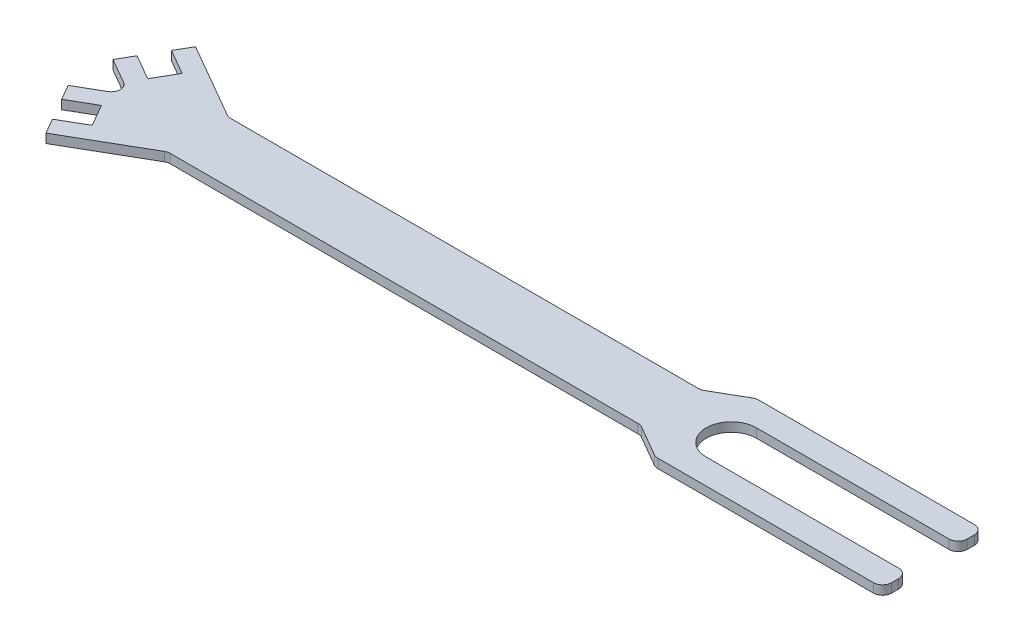
SolidWorks part; units mm, degrees
ref_plane "Front Plane" through (0, 0, 0) normal (0, 0, 1) x (1, 0, 0)
ref_plane "Top Plane" through (0, 0, 0) normal (0, 1, 0) x (1, 0, 0)
ref_plane "Right Plane" through (0, 0, 0) normal (1, 0, 0) x (0, 0, -1)
sketch "Sketch1" plane through (0, 0, 0) normal (0, 1, 0) x (1, 0, 0)
  line L0 (-363.1089, 480) -> (-363.1089, -480)
  line L1 (-363.1089, -480) -> (-303.1089, -480)
  line L2 (-303.1089, -480) -> (-303.1089, -400)
  line L3 (-303.1089, -400) -> (303.1089, -50)
  line L4 (303.1089, -50) -> (1036.8911, -50)
  line L5 (1036.8911, -50) -> (1036.8911, 50) construction
  line L6 (1036.8911, 50) -> (303.1089, 50)
  line L7 (303.1089, 50) -> (-303.1089, 400)
  line L8 (-303.1089, 400) -> (-303.1089, 480)
  line L9 (-303.1089, 480) -> (-363.1089, 480)
  line L10 (-363.1089, 0) -> (1036.8911, 0) construction
  line L11 (0, 225) -> (0, -225) construction
  line L14 (1036.8911, 50) -> (1066.8911, 50)
  line L15 (1036.8911, 50) -> (1036.8911, -50) construction
  line L16 (1036.8911, -50) -> (1066.8911, -50)
  line L17 (1066.8911, 50) -> (1066.8911, -50)
  dimension "D1" = 960
  dimension "D2" = 60
  dimension "D3" = 100
  dimension "D4" = 1400
  dimension "D5" = 150
  dimension "D6" = 80
  dimension "D7" = 30
extrude "Boss-Extrude1" add sketch "Sketch1" along normal blind 9
sketch "Sketch2" plane through (0, 9, 0) normal (0, 1, 0) x (1, 0, 0)
  line L1 (-363.1089, 480) -> (-303.1089, 480)
  line L2 (-363.1089, 480) -> (-363.1089, 400)
  line L3 (-363.1089, 400) -> (-303.1089, 400)
  line L4 (-303.1089, 480) -> (-303.1089, 400)
  line L5 (-363.1089, -480) -> (-303.1089, -480)
  line L6 (-363.1089, -480) -> (-363.1089, -400)
  line L7 (-363.1089, -400) -> (-303.1089, -400)
  line L8 (-303.1089, -480) -> (-303.1089, -400)
extrude "Boss-Extrude2" add sketch "Sketch2" along normal blind 500
sketch "Sketch3" plane through (0, 0, 0) normal (0, 0, 1) x (1, 0, 0)
  line L0 (-333.1089, 509) -> (-333.1089, 254.2) construction
  line L1 (-363.1089, 509) -> (-303.1089, 509) construction
  line L2 (-333.1089, 254.2) -> (-333.1089, 25) construction
  line L3 (-333.1089, 25) -> (-333.1089, 0) construction
  line L4 (-363.1089, 0) -> (-303.1089, 0) construction
  line L6 (-363.1089, 509) -> (-303.1089, 509)
  line L7 (-363.1089, 509) -> (-363.1089, 9)
  line L8 (-363.1089, 9) -> (-303.1089, 9)
  line L9 (-303.1089, 509) -> (-303.1089, 9)
  circle A0 centre (-333.1089, 254.2) radius 229.2
  circle A1 centre (-333.1089, 254.2) radius 6
  circle A2 centre (-333.1089, 254.2) radius 30
  dimension "D1" = 458.4
  dimension "D3" = 12
  dimension "D2" = 25
extrude "Cut-Extrude1" cut sketch "Sketch3" against normal through all both and the other way through all contours A2 L9 A0 L7 | A0 L9 L6 L7 | A1 region at (-333.1089, 495.8654, 0) region at (-333.1089, 380.1444, 0) region at (-333.1089, 254.2, 0)
sketch "Sketch4" plane through (0, 9, 0) normal (0, 1, 0) x (1, 0, 0)
  line L0 (866.8911, 25) -> (1066.8911, 25)
  line L2 (866.8911, -25) -> (1066.8911, -25)
  line L3 (1066.8911, -25) -> (1066.8911, 25)
  line L4 (866.8911, 0) -> (1066.8911, 0) construction
  line L5 (1066.8911, -50) -> (1066.8911, 50) construction
  circle A0 centre (866.8911, 0) radius 25
  dimension "D1" = 50
  dimension "D2" = 200
extrude "Cut-Extrude2" cut sketch "Sketch4" against normal through all contours L4 A0 L2 | A0 L4 L3 L0 | A0 region at (976.6223, 9, -12.7057) region at (884.0688, 9, -17.1777) region at (976.6223, 9, 12.7057)
sketch "Sketch16" plane through (0, 0, 0) normal (0, 0, 1) x (1, 0, 0)
  line L0 (-359.656, 240.2268) -> (-348.1089, 218.2888)
  line L5 (-348.1089, 218.2888) -> (-348.1089, 24)
  line L7 (-363.1089, 9) -> (-288.1089, 9)
  line L8 (303.1089, 9) -> (-303.1089, 9) construction
  line L9 (-303.1089, 254.2) -> (-303.1089, 24)
  line L10 (-348.1089, 24) -> (-363.1089, 9)
  line L11 (-303.1089, 254.2) -> (-303.1089, 9) construction
  line L12 (-303.1089, 24) -> (-288.1089, 9)
  line L13 (-348.1089, 24) -> (-303.1089, 24) construction
  line L14 (-346.3825, 247.2134) -> (-358.4836, 270.2039)
  line L15 (-319.8353, 261.1866) -> (-331.9364, 284.1771)
  circle A0 centre (-333.1089, 254.2) radius 15
  circle A1 centre (-333.1089, 254.2) radius 30
  arc A2 (-303.1089, 254.2) -> (-363.1089, 254.2) centre (-333.1089, 254.2) ccw construction
  circle A3 centre (-360.6089, 215.2) radius 12.5 construction
  dimension "D1" = 30
  dimension "D4" = 25
  dimension "D2" = 45
  dimension "D3" = 45
extrude "Boss-Extrude8" add sketch "Sketch16" along normal blind 305 and the other way blind 305 contours A1 L0 L5 L10 L7 L12 L9 | A1 L15 A0 L14 region at (-325.4564, 117.1914, 0) region at (-362.2383, 255.3393, 0)
sketch "Sketch17" plane through (0, 0, 0) normal (1, 0, 0) x (0, 0, -1)
  line L1 (230, 309) -> (-230, 309)
  line L2 (230, 309) -> (230, 9)
  line L3 (230, 9) -> (-230, 9)
  line L4 (-230, 309) -> (-230, 9)
  line L5 (0, 0) -> (0, 309) construction
  line L6 (480, 0) -> (-480, 0) construction
  dimension "D1" = 460
  dimension "D2" = 9
  dimension "D3" = 300
extrude "Cut-Extrude9" cut sketch "Sketch17" against normal through all
sketch "Sketch7" plane through (0, 0, 0) normal (1, 0, 0) x (0, 0, -1)
  line L1 (480, 284.2) -> (230, 284.2)
  line L2 (480, 284.2) -> (480, 9)
  line L3 (480, 9) -> (230, 9)
  line L4 (230, 284.2) -> (230, 9)
  line L5 (230, 218.2888) -> (230, 24) construction
  line L6 (471, 146.6) -> (444.5, 146.6) construction
  line L7 (480, 284.2) -> (471, 284.2)
  line L8 (480, 284.2) -> (480, 9)
  line L9 (480, 9) -> (471, 9)
  line L10 (471, 284.2) -> (471, 9)
  line L11 (400, 9) -> (409, 9)
  line L12 (400, 9) -> (400, 284.2)
  line L13 (400, 284.2) -> (409, 284.2)
  line L14 (409, 9) -> (409, 284.2)
  line L15 (444.5, 284.2) -> (435.5, 284.2)
  line L16 (444.5, 284.2) -> (444.5, 9)
  line L17 (444.5, 9) -> (435.5, 9)
  line L18 (435.5, 284.2) -> (435.5, 9)
  line L19 (444.5, 146.6) -> (435.5, 146.6) construction
  line L20 (435.5, 146.6) -> (409, 146.6) construction
  line L22 (0, 274.5241) -> (0, -136.9768) construction
  line L23 (-435.5, 146.6) -> (-409, 146.6) construction
  line L24 (305, 284.2) -> (296, 284.2)
  line L25 (305, 284.2) -> (305, 9)
  line L26 (305, 9) -> (296, 9)
  line L27 (296, 284.2) -> (296, 9)
  line L28 (239, 9) -> (230, 9)
  line L29 (239, 9) -> (239, 284.2)
  line L30 (239, 284.2) -> (230, 284.2)
  line L31 (230, 9) -> (230, 284.2)
  line L32 (-444.5, 146.6) -> (-435.5, 146.6) construction
  line L33 (-471, 146.6) -> (-444.5, 146.6) construction
  line L34 (-230, 9) -> (-230, 284.2)
  line L35 (-239, 284.2) -> (-230, 284.2)
  line L36 (-239, 9) -> (-239, 284.2)
  line L37 (-239, 9) -> (-230, 9)
  line L38 (-296, 284.2) -> (-296, 9)
  line L39 (-305, 9) -> (-296, 9)
  line L40 (-305, 284.2) -> (-305, 9)
  line L41 (-305, 284.2) -> (-296, 284.2)
  line L42 (-435.5, 284.2) -> (-435.5, 9)
  line L43 (-444.5, 9) -> (-435.5, 9)
  line L44 (-444.5, 284.2) -> (-444.5, 9)
  line L45 (-444.5, 284.2) -> (-435.5, 284.2)
  line L46 (-409, 9) -> (-409, 284.2)
  line L47 (-400, 284.2) -> (-409, 284.2)
  line L48 (-400, 9) -> (-400, 284.2)
  line L49 (-400, 9) -> (-409, 9)
  line L50 (-471, 284.2) -> (-471, 9)
  line L51 (-480, 9) -> (-471, 9)
  line L52 (-480, 284.2) -> (-480, 9)
  line L53 (-480, 284.2) -> (-471, 284.2)
  line L54 (-230, 284.2) -> (-230, 9)
  line L55 (-480, 9) -> (-230, 9)
  line L56 (-480, 284.2) -> (-480, 9)
  line L57 (-480, 284.2) -> (-230, 284.2)
  line L58 (305, 218.2888) -> (305, 24) construction
  dimension "D1" = 9
  dimension "D2" = 9
  dimension "D3" = 9
  dimension "D4" = 9
  dimension "D5" = 9
extrude "Cut-Extrude4" cut sketch "Sketch7" against normal through all both and the other way through all contours L1 L16 L3 L10 | L18 L1 L14 L3 | L29 L3 L27 L1 | L57 L38 L55 L36 | L57 L42 L55 L46 | L57 L50 L55 L44 | L1 L18 L3 L16 | L45 L44 L43 L42 region at (0, 146.6, -457.75) region at (0, 146.6, -440) region at (0, 146.6, -422.25) region at (0, 146.6, -267.5) region at (0, 146.6, 267.5) region at (0, 146.6, 422.25) region at (0, 146.6, 440) region at (0, 146.6, 457.75)
sketch "Sketch10" plane through (0, 9, 0) normal (0, 1, 0) x (1, 0, 0)
  line L0 (-363.1089, 221) -> (-113.0718, 221)
  line L2 (-113.0718, 221) -> (269.7114, 0)
  line L3 (269.7114, 0) -> (-113.0718, -221)
  line L4 (-113.0718, -221) -> (-363.1089, -221)
  line L5 (-363.1089, -221) -> (-363.1089, 221)
  line L6 (0, 0) -> (269.7114, 0) construction
  line L7 (-363.1089, 0) -> (0, 0) construction
  line L8 (-113.0718, -221) -> (-113.0718, 221) construction
  line L9 (303.1089, 50) -> (-303.1089, 400) construction
  line L10 (-363.1089, -230) -> (-363.1089, 230) construction
  line L11 (303.1089, 50) -> (337.7499, 30)
  line L12 (337.7499, 30) -> (806.8911, 30)
  line L13 (806.8911, 30) -> (841.5321, 50)
  line L14 (1066.8911, 50) -> (303.1089, 50) construction
  line L15 (841.5321, 50) -> (303.1089, 50)
  line L16 (303.1089, -50) -> (337.7499, -30)
  line L17 (337.7499, -30) -> (806.8911, -30)
  line L18 (806.8911, -30) -> (841.5321, -50)
  line L19 (303.1089, -50) -> (1066.8911, -50) construction
  line L20 (841.5321, -50) -> (303.1089, -50)
  line L21 (337.7499, -30) -> (337.7499, 30) construction
  line L22 (269.7114, 0) -> (337.7499, 0) construction
  line L23 (806.8911, 30) -> (806.8911, -30) construction
  line L24 (-303.1089, -400) -> (303.1089, -50) construction
  line L25 (841.5321, 50) -> (841.5321, -50) construction
  line L27 (-363.1089, 230) -> (-288.1089, 230) construction
  line L28 (-363.1089, -230) -> (-288.1089, -230) construction
  arc A0 (866.8911, 25) -> (866.8911, -25) centre (866.8911, 0) ccw construction
  dimension "D1" = 60
  dimension "D2" = 30
  dimension "D3" = 60
  dimension "D4" = 60
  dimension "D5" = 9
  dimension "D6" = 9
extrude "Cut-Extrude6" cut sketch "Sketch10" against normal through all
sketch "Sketch11" plane through (-363.1089, 0, 0) normal (-1, 0, 0) x (0, 0, 1)
  line L0 (-480, 254.2) -> (-480, 0) construction
  line L1 (-480, 224.2) -> (-400, 224.2)
  line L2 (-480, 224.2) -> (-480, 215.2)
  line L3 (-480, 215.2) -> (-400, 215.2)
  line L4 (-400, 224.2) -> (-400, 215.2)
  line L5 (-400, 254.2) -> (-400, 9) construction
  line L6 (400, 254.2) -> (400, 9) construction
  line L7 (400, 224.2) -> (480, 224.2)
  line L8 (400, 224.2) -> (400, 215.2)
  line L9 (400, 215.2) -> (480, 215.2)
  line L10 (480, 224.2) -> (480, 215.2)
  line L11 (480, 254.2) -> (480, 0) construction
  line L12 (-400, 224.2) -> (400, 224.2) construction
  line L13 (400, 215.2) -> (-400, 215.2) construction
  line L14 (-400, 284.2) -> (-409, 284.2) construction
  dimension "D1" = 9
  dimension "D2" = 60
extrude "Boss-Extrude5" add sketch "Sketch11" against normal up to surface (60 mm away) up to face at (-303.1089, 115.9778, 435.5556)
sketch "Sketch18" plane through (-348.1089, 0, 0) normal (-1, 0, 0) x (0, 0, 1)
  line L0 (-230, 218.2888) -> (-230, 24) construction
  line L1 (-305, 218.2888) -> (-230, 218.2888)
  line L2 (-305, 218.2888) -> (-305, 209.2888)
  line L3 (-305, 209.2888) -> (-230, 209.2888)
  line L4 (-230, 218.2888) -> (-230, 209.2888)
  line L5 (230, 24) -> (230, 218.2888) construction
  line L6 (305, 218.2888) -> (230, 218.2888)
  line L7 (305, 218.2888) -> (305, 209.2888)
  line L8 (305, 209.2888) -> (230, 209.2888)
  line L9 (230, 218.2888) -> (230, 209.2888)
  dimension "D1" = 9
  dimension "D2" = 9
extrude "Boss-Extrude9" add sketch "Sketch18" against normal up to surface (45 mm away) up to face at (-303.1089, 139.1, -234.5)
sketch "Sketch12" plane through (0, 9, 0) normal (0, 1, 0) x (1, 0, 0)
  line L0 (-363.1089, -480) -> (-303.1089, -480) construction
  line L1 (-363.1089, 480) -> (-303.1089, 480)
  line L2 (-363.1089, 480) -> (-363.1089, 489)
  line L3 (-363.1089, 489) -> (-303.1089, 489)
  line L4 (-303.1089, 480) -> (-303.1089, 489)
  line L5 (-363.1089, -480) -> (-303.1089, -480)
  line L6 (-363.1089, -480) -> (-363.1089, -489)
  line L7 (-363.1089, -489) -> (-303.1089, -489)
  line L8 (-303.1089, -480) -> (-303.1089, -489)
  dimension "D1" = 9
  dimension "D2" = 9
extrude "Boss-Extrude6" add sketch "Sketch12" against normal blind 9
fillet "Fillet3" radius 9 27 edges at (-303.1089, 4.5, -489) (-363.1089, 4.5, -489) (-363.1089, 4.5, -221) (-363.1089, 4.5, 221) (-363.1089, 4.5, 489) (-303.1089, 4.5, 489) (841.5321, 4.5, 50) (806.8911, 4.5, 30) (841.5321, 4.5, -50) (806.8911, 4.5, -30) (337.7499, 4.5, -30) (337.7499, 4.5, 30) (269.7114, 4.5, 0) (-113.0718, 4.5, 221) (-113.0718, 4.5, -221) (-303.1089, 24, -234.5) (-303.1089, 24, -300.5) (-303.1089, 24, 234.5) (-303.1089, 24, 300.5) (-348.1089, 24, 234.5) (-348.1089, 24, 300.5) (-348.1089, 24, -234.5) (-348.1089, 24, -300.5) (1066.8911, 4.5, 50) (1066.8911, 4.5, 25) (1066.8911, 4.5, -25) (1066.8911, 4.5, -50)
sketch "Sketch15" plane through (0, 9, 0) normal (0, 1, 0) x (1, 0, 0)
  line L0 (-83.154, 230) -> (-83.154, -230)
  line L1 (-113.154, 230) -> (-113.154, 220.6933) construction
  line L2 (-363.1089, 230) -> (-288.1089, 230) construction
  line L4 (-83.154, -230) -> (-143.154, -230)
  line L5 (-143.154, -230) -> (-143.154, 230)
  line L6 (-143.154, 230) -> (-83.154, 230)
  line L7 (0, 0) -> (-83.154, 0) construction
  arc A0 (-110.9833, 219.7942) -> (-115.4833, 221) centre (-115.4833, 212) ccw construction
  dimension "D1" = 60
extrude "Boss-Extrude7" add sketch "Sketch15" against normal blind 9
fillet "Fillet4" radius 9 4 edges at (-83.154, 4.5, -203.7269) (-83.154, 4.5, 203.7269) (-143.154, 4.5, 221) (-143.154, 4.5, -221)
sketch "Sketch20" plane through (0, 9, 0) normal (0, 1, 0) x (1, 0, 0)
  line L0 (-348.1089, 480) -> (-348.1089, 400)
  line L1 (-363.1089, 480) -> (-303.1089, 480)
  line L2 (-363.1089, 480) -> (-363.1089, 471)
  line L3 (-363.1089, 471) -> (-303.1089, 471)
  line L4 (-303.1089, 480) -> (-303.1089, 471)
  line L5 (-363.1089, 409) -> (-303.1089, 409)
  line L6 (-363.1089, 409) -> (-363.1089, 400)
  line L7 (-363.1089, 400) -> (-303.1089, 400)
  line L8 (-303.1089, 409) -> (-303.1089, 400)
  line L9 (-363.1089, 305) -> (-288.1089, 305)
  line L10 (-363.1089, 305) -> (-363.1089, 296)
  line L11 (-363.1089, 296) -> (-288.1089, 296)
  line L12 (-288.1089, 305) -> (-288.1089, 296)
  line L13 (-363.1089, 239) -> (-288.1089, 239)
  line L14 (-363.1089, 239) -> (-363.1089, 230)
  line L15 (-363.1089, 230) -> (-288.1089, 230)
  line L16 (-288.1089, 239) -> (-288.1089, 230)
  line L17 (-318.1089, 480) -> (-318.1089, 400)
  line L18 (-363.1089, 440) -> (-348.1089, 440) construction
  line L19 (-363.1089, 409) -> (-363.1089, 471) construction
  line L20 (-348.1089, 440) -> (-318.1089, 440) construction
  line L21 (-318.1089, 440) -> (-303.1089, 440) construction
  line L22 (-303.1089, 471) -> (-303.1089, 409) construction
  line L23 (-340.6089, 305) -> (-340.6089, 230)
  line L24 (-310.6089, 305) -> (-310.6089, 230)
  line L25 (-288.1089, 296) -> (-288.1089, 239) construction
  line L26 (-363.1089, 267.5) -> (-340.6089, 267.5) construction
  line L27 (-363.1089, 296) -> (-363.1089, 239) construction
  line L28 (-340.6089, 267.5) -> (-310.6089, 267.5) construction
  line L29 (-310.6089, 267.5) -> (-288.1089, 267.5) construction
  line L30 (-512.4702, 0) -> (462.9433, 0) construction
  line L31 (-310.6089, -267.5) -> (-288.1089, -267.5) construction
  line L32 (-340.6089, -267.5) -> (-310.6089, -267.5) construction
  line L33 (-363.1089, -267.5) -> (-340.6089, -267.5) construction
  line L34 (-288.1089, -296) -> (-288.1089, -239) construction
  line L35 (-318.1089, -440) -> (-303.1089, -440) construction
  line L36 (-348.1089, -440) -> (-318.1089, -440) construction
  line L37 (-363.1089, -440) -> (-348.1089, -440) construction
  line L38 (-310.6089, -305) -> (-310.6089, -230)
  line L39 (-340.6089, -305) -> (-340.6089, -230)
  line L40 (-318.1089, -480) -> (-318.1089, -400)
  line L41 (-288.1089, -239) -> (-288.1089, -230)
  line L42 (-363.1089, -230) -> (-288.1089, -230)
  line L43 (-363.1089, -239) -> (-363.1089, -230)
  line L44 (-363.1089, -239) -> (-288.1089, -239)
  line L45 (-288.1089, -305) -> (-288.1089, -296)
  line L46 (-363.1089, -296) -> (-288.1089, -296)
  line L47 (-363.1089, -305) -> (-363.1089, -296)
  line L48 (-363.1089, -305) -> (-288.1089, -305)
  line L49 (-303.1089, -409) -> (-303.1089, -400)
  line L50 (-363.1089, -400) -> (-303.1089, -400)
  line L51 (-363.1089, -409) -> (-363.1089, -400)
  line L52 (-363.1089, -409) -> (-303.1089, -409)
  line L53 (-303.1089, -480) -> (-303.1089, -471)
  line L54 (-363.1089, -471) -> (-303.1089, -471)
  line L55 (-363.1089, -480) -> (-363.1089, -471)
  line L56 (-363.1089, -480) -> (-303.1089, -480)
  line L57 (-348.1089, -480) -> (-348.1089, -400)
  dimension "D1" = 30
  dimension "D2" = 30
sketch "Sketch21" plane through (0, 9, 0) normal (0, 1, 0) x (1, 0, 0)
  line L0 (1066.8911, 34) -> (1066.8911, 41) construction
  line L1 (-363.1089, 489) -> (1066.8911, 489)
  line L2 (-363.1089, 489) -> (-363.1089, -489)
  line L3 (-363.1089, -489) -> (1066.8911, -489)
  line L4 (1066.8911, 489) -> (1066.8911, -489)
  line L5 (-354.1089, -489) -> (-312.1089, -489) construction
  line L6 (-363.1089, -305) -> (-363.1089, -400) construction
  line L7 (-312.1089, 489) -> (-354.1089, 489) construction
extrude "Cut-Extrude11" cut sketch "Sketch20" against normal through all both and the other way through all contours L56 L57 L54 L55 | L40 L56 L53 L54 | L52 L57 L50 L51 | L40 L52 L49 L50 | L47 L48 L39 L46 | L38 L48 L45 L46 | L38 L44 L41 L42 | L43 L44 L39 L42 | L23 L13 L14 L15 | L13 L24 L15 L16 | L9 L24 L11 L12 | L23 L9 L10 L11 | L6 L7 L0 L5 | L5 L17 L7 L8 | L1 L17 L3 L4 | L2 L3 L0 L1 region at (-355.6089, 9, -475.5) region at (-310.6089, 9, -475.5) region at (-355.6089, 9, -404.5) region at (-310.6089, 9, -404.5) region at (-351.8589, 9, -300.5) region at (-299.3589, 9, -300.5) region at (-351.8589, 9, -234.5) region at (-299.3589, 9, -234.5) region at (-299.3589, 9, 300.5) region at (-351.8589, 9, 300.5) region at (-299.3589, 9, 234.5) region at (-351.8589, 9, 234.5) region at (-310.6089, 9, 475.5) region at (-355.6089, 9, 475.5) region at (-310.6089, 9, 404.5) region at (-355.6089, 9, 404.5)
extrude "Cut-Extrude12" cut sketch "Sketch21" along normal through all
sketch "Sketch22" plane through (0, 9, 0) normal (0, 1, 0) x (1, 0, 0)
  line L0 (1066.8911, 34) -> (1066.8911, 41) construction
  line L1 (-363.1089, -489) -> (1066.8911, -489)
  line L2 (-363.1089, -489) -> (-363.1089, 489)
  line L3 (-363.1089, 489) -> (1066.8911, 489)
  line L4 (1066.8911, -489) -> (1066.8911, 489)
  line L5 (-312.1089, 489) -> (-354.1089, 489) construction
  line L6 (-363.1089, 471) -> (-363.1089, 409) construction
  line L7 (-354.1089, -489) -> (-312.1089, -489) construction
  line L8 (-83.154, 188.1385) -> (-143.154, 188.1385)
  line L9 (-143.154, 212) -> (-143.154, -212) construction
  line L10 (-113.154, 188.1385) -> (-113.154, 213.1385) construction
  line L11 (-69.654, 195.9327) -> (-69.654, 265.2147)
  line L12 (-125.654, 188.1385) -> (-100.654, 188.1385)
  line L13 (256.2114, 7.7942) -> (286.2114, 59.7558)
  line L14 (256.2114, 7.7942) -> (231.2114, 22.228)
  line L15 (231.2114, 22.228) -> (239.9614, 37.3834)
  line L16 (335.6615, 31.2058) -> (-303.1089, 400) construction
  line L17 (256.2114, 7.7942) -> (256.2114, -7.7942)
  line L18 (-69.654, 265.2147) -> (-297.5196, 489)
  line L19 (-143.154, 188.1385) -> (-363.1089, 188.1385)
  line L20 (340.1615, 88.1184) -> (-69.654, 265.2147)
  line L21 (340.1615, 88.1184) -> (1066.8911, 88.1184)
  line L22 (194.4241, 7.7942) -> (-83.154, 188.1385)
  line L23 (-69.654, 195.9327) -> (-83.154, 188.1385)
  line L24 (-125.654, 188.1385) -> (-125.654, 213.1385)
  line L25 (-125.654, 213.1385) -> (-100.654, 213.1385)
  line L26 (-100.654, 188.1385) -> (-100.654, 213.1385)
  line L27 (-69.654, 195.9327) -> (-44.654, 181.4989)
  line L28 (256.2114, 7.7942) -> (-69.654, 195.9327) construction
  line L29 (-44.654, 181.4989) -> (-44.654, 203.64)
  line L30 (-44.654, 203.64) -> (-69.654, 218.0737)
  line L32 (-69.654, 265.2147) -> (-44.654, 250.781)
  line L33 (-44.654, 250.781) -> (-44.654, 228.64)
  line L34 (-44.654, 228.64) -> (-69.654, 243.0737)
  line L35 (-44.654, 203.64) -> (-44.654, 228.64)
  line L36 (239.9614, 37.3834) -> (264.9614, 22.9497)
  line L37 (239.9614, 37.3834) -> (252.4614, 59.0341)
  line L38 (252.4614, 59.0341) -> (277.4614, 44.6003)
  line L39 (252.4614, 59.0341) -> (261.2114, 74.1895)
  line L40 (261.2114, 74.1895) -> (286.2114, 59.7558)
  line L41 (194.4241, 7.7942) -> (256.2114, 7.7942)
  line L42 (286.2114, 59.7558) -> (340.1615, 88.1184)
  line L43 (-181.378, 0) -> (-33.8367, 0) construction
  line L44 (-113.154, -188.1385) -> (-113.154, -213.1385) construction
  line L45 (286.2114, -59.7558) -> (340.1615, -88.1184)
  line L46 (194.4241, -7.7942) -> (256.2114, -7.7942)
  line L47 (261.2114, -74.1895) -> (286.2114, -59.7558)
  line L48 (252.4614, -59.0341) -> (261.2114, -74.1895)
  line L49 (252.4614, -59.0341) -> (277.4614, -44.6003)
  line L50 (239.9614, -37.3834) -> (252.4614, -59.0341)
  line L51 (239.9614, -37.3834) -> (264.9614, -22.9497)
  line L52 (-44.654, -203.64) -> (-44.654, -228.64)
  line L53 (-44.654, -228.64) -> (-69.654, -243.0737)
  line L54 (-44.654, -250.781) -> (-44.654, -228.64)
  line L55 (-69.654, -265.2147) -> (-44.654, -250.781)
  line L56 (-44.654, -203.64) -> (-69.654, -218.0737)
  line L57 (-44.654, -181.4989) -> (-44.654, -203.64)
  line L58 (-69.654, -195.9327) -> (-44.654, -181.4989)
  line L59 (-100.654, -188.1385) -> (-100.654, -213.1385)
  line L60 (-125.654, -213.1385) -> (-100.654, -213.1385)
  line L61 (-125.654, -188.1385) -> (-125.654, -213.1385)
  line L62 (-69.654, -195.9327) -> (-83.154, -188.1385)
  line L63 (194.4241, -7.7942) -> (-83.154, -188.1385)
  line L64 (340.1615, -88.1184) -> (1066.8911, -88.1184)
  line L65 (340.1615, -88.1184) -> (-69.654, -265.2147)
  line L66 (-143.154, -188.1385) -> (-363.1089, -188.1385)
  line L67 (-69.654, -265.2147) -> (-297.5196, -489)
  line L68 (231.2114, -22.228) -> (239.9614, -37.3834)
  line L69 (256.2114, -7.7942) -> (231.2114, -22.228)
  line L70 (256.2114, -7.7942) -> (286.2114, -59.7558)
  line L71 (-125.654, -188.1385) -> (-100.654, -188.1385)
  line L72 (-69.654, -195.9327) -> (-69.654, -265.2147)
  line L73 (-83.154, -188.1385) -> (-143.154, -188.1385)
  line L74 (-363.1089, -489) -> (1066.8911, -489)
  line L75 (194.4241, -7.7942) -> (194.4241, 7.7942)
  dimension "D1" = 25
  dimension "D2" = 25
  dimension "D3" = 25
  dimension "D4" = 25
  dimension "D5" = 25
  dimension "D6" = 25
extrude "Cut-Extrude13" cut sketch "Sketch22" against normal through all contours L69 L46 L63 L62 L58 L57 L52 L54 L55 L65 L45 L47 L48 L50 L68 | L40 L42 L20 L32 L33 L35 L29 L27 L23 L22 L41 L14 L15 L37 L39 | L70 L51 L50 L49 | L38 L37 L36 L13 region at (122.7349, 9, 124.6322) region at (122.7349, 9, -124.6322) region at (258.7114, 9, 40.9919) region at (258.7114, 9, -40.9919)
